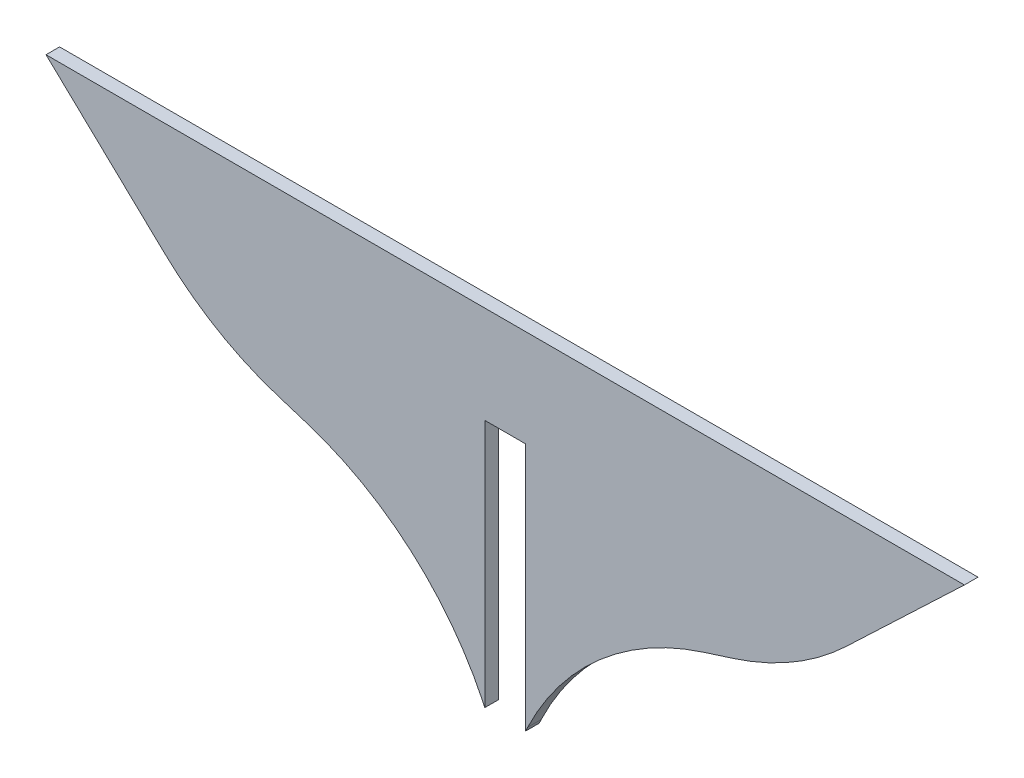
SolidWorks part; units mm, degrees
ref_plane "Plan de face" through (0, 0, 0) normal (0, 0, 1) x (1, 0, 0)
ref_plane "Plan de dessus" through (0, 0, 0) normal (0, 1, 0) x (1, 0, 0)
ref_plane "Plan de droite" through (0, 0, 0) normal (1, 0, 0) x (0, 0, -1)
sketch "Esquisse1" plane through (0, 0, 0) normal (0, 0, 1) x (1, 0, 0)
  line L5 (11.9172, -63.8757) -> (11.9172, -8.8757)
  line L6 (11.9172, -8.8757) -> (2.9172, -8.8757)
  line L7 (7.4172, -8.8757) -> (7.4172, 12.6243) construction
  line L8 (2.9172, -63.8757) -> (2.9172, -8.8757)
  line L19 (-94.1134, 12.6243) -> (108.9478, 12.6243)
  line L20 (11.9172, -63.8757) -> (24.5198, -37.6377)
  line L21 (24.5198, -37.6377) -> (72.012, -22.4721)
  line L22 (72.012, -22.4721) -> (108.9478, 12.6243)
  line L23 (-57.1776, -22.4721) -> (-94.1134, 12.6243)
  line L24 (-9.6854, -37.6377) -> (-57.1776, -22.4721)
  line L25 (2.9172, -63.8757) -> (-9.6854, -37.6377)
  point P10 (7.4172, 12.6243)
  point P13 (7.4172, 12.6243)
  dimension "D1" = 21.5
  dimension "D5" = 9
  dimension "D7" = 55
extrude "Boss.-Extru.1" add sketch "Esquisse1" along normal blind 3
fillet "Congé1" radius 65 4 edges at (72.012, -22.4721, 1.5) (24.5198, -37.6377, 1.5) (-57.1776, -22.4721, 1.5) (-9.6854, -37.6377, 1.5)
